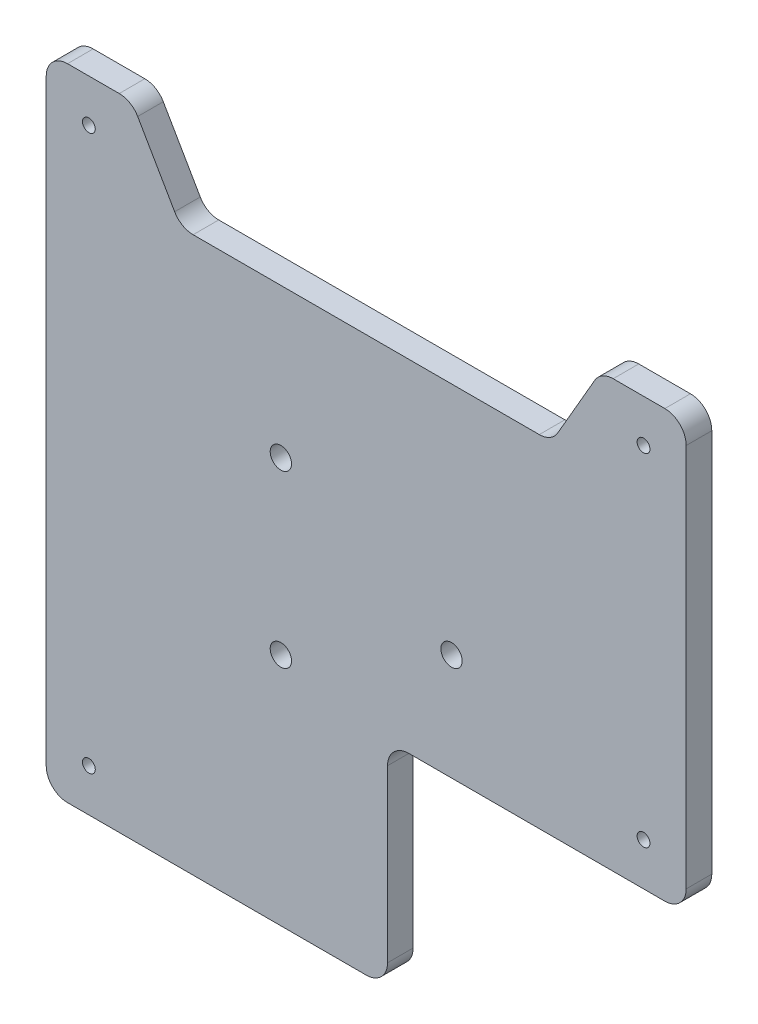
SolidWorks part; units mm, degrees
ref_plane "Plano frontal" through (0, 0, 0) normal (0, 0, 1) x (1, 0, 0)
ref_plane "Plano superior" through (0, 0, 0) normal (0, 1, 0) x (1, 0, 0)
ref_plane "Plano direito" through (0, 0, 0) normal (1, 0, 0) x (0, 0, -1)
sketch "Esboço1" plane through (0, 0, 0) normal (0, 0, 1) x (1, 0, 0)
  line L1 (-138.7501, 120.054) -> (11.2499, 120.054)
  line L2 (-138.7501, 120.054) -> (-138.7501, -29.946)
  line L3 (-138.7501, -29.946) -> (11.2499, -29.946)
  line L4 (11.2499, 120.054) -> (11.2499, -29.946)
  line L5 (-138.7501, 120.054) -> (11.2499, -29.946) construction
  line L6 (-138.7501, -29.946) -> (11.2499, 120.054) construction
  line L7 (-83.7501, 65.054) -> (-43.7501, 65.054) construction
  line L8 (-83.7501, 65.054) -> (-83.7501, 25.054) construction
  line L9 (-83.7501, 25.054) -> (-43.7501, 25.054) construction
  line L10 (-43.7501, 65.054) -> (-43.7501, 25.054) construction
  line L11 (-83.7501, 65.054) -> (-43.7501, 25.054) construction
  line L12 (-83.7501, 25.054) -> (-43.7501, 65.054) construction
  circle A0 centre (-83.7501, 65.054) radius 2.5
  circle A3 centre (-83.7501, 25.054) radius 2.5
  circle A4 centre (-43.7501, 45.054) radius 2.5
  point P0 (-63.7501, 45.054)
  dimension "D4" = 5
  dimension "D1" = 150
  dimension "D2" = 40
  dimension "D3" = 40
extrude "Ressalto-extrusão1" add sketch "Esboço1" along normal blind 6
ref_axis "Eixo1" through (-83.7501, 65.054, 6) along (0, 0, -1)
ref_axis "Eixo2" through (-83.7501, 25.054, 6) along (0, 0, -1)
ref_axis "Eixo3" through (-43.7501, 45.054, 6) along (0, 0, -1)
ref_plane "Plano1" through (-83.7501, 0, 0) normal (-1, 0, 0) x (0, 0, 1)
ref_plane "Plano2" through (-43.7501, 0, 0) normal (-1, 0, 0) x (0, 0, 1)
ref_plane "Plano3" through (-63.7501, 0, 0) normal (-1, 0, 0) x (0, 0, 1)
sketch "Esboço2" plane through (0, 0, 6) normal (0, 0, 1) x (1, 0, 0)
  line L2 (11.2499, 100.054) -> (-138.7501, 100.054)
  line L3 (11.2499, 100.054) -> (-138.7501, 100.054) construction
  line L5 (-118.7501, 120.054) -> (-118.7501, -29.946)
  line L6 (-118.7501, 120.054) -> (-118.7501, -29.946) construction
  line L7 (-8.7501, 120.054) -> (-20.2971, 100.054)
  line L8 (-8.7501, -29.946) -> (-8.7501, 120.054)
  line L9 (-8.7501, -29.946) -> (-8.7501, 120.054) construction
  line L10 (-118.7501, 120.054) -> (-107.2031, 100.054)
  line L11 (-20.2971, 100.054) -> (-107.2031, 100.054)
  line L12 (-8.7501, 120.054) -> (-118.7501, 120.054)
  dimension "D4" = 30
  dimension "D5" = 30
  dimension "D1" = 20
  dimension "D2" = 20
  dimension "D3" = 20
extrude "Corte-extrusão1" cut sketch "Esboço2" against normal up to surface (6 mm away) up to face at (-63.7501, 45.054, 0)
sketch "Esboço3" plane through (0, 0, 6) normal (0, 0, 1) x (1, 0, 0)
  line L2 (-138.7501, 20.054) -> (11.2499, 20.054)
  line L3 (-138.7501, 20.054) -> (11.2499, 20.054) construction
  line L5 (-58.7501, -29.946) -> (-58.7501, 120.054)
  line L6 (-58.7501, -29.946) -> (-58.7501, 120.054) construction
  line L7 (-58.7501, 20.054) -> (11.2499, 20.054)
  line L8 (-58.7501, 20.054) -> (-58.7501, -29.946)
  line L9 (-58.7501, -29.946) -> (11.2499, -29.946)
  line L10 (11.2499, 20.054) -> (11.2499, -29.946)
  dimension "D1" = 50
  dimension "D2" = 70
extrude "Corte-extrusão2" cut sketch "Esboço3" against normal up to surface (6 mm away) up to face at (-63.7501, 77.554, 0)
fillet "Filete1" radius 5 10 edges at (11.2499, 20.054, 3) (-138.7501, -29.946, 3) (11.2499, 120.054, 3) (-138.7501, 120.054, 3) (-58.7501, -29.946, 3) (-58.7501, 20.054, 3) (-118.7501, 120.054, 3) (-20.2971, 100.054, 3) (-107.2031, 100.054, 3) (-8.7501, 120.054, 3)
sketch "Esboço4" plane through (0, 0, 6) normal (0, 0, 1) x (1, 0, 0)
  line L20 (-128.7501, -19.946) -> (-68.7501, -19.946)
  line L21 (-68.7501, -19.946) -> (-68.7501, 15.054)
  line L22 (-53.7501, 30.054) -> (1.2499, 30.054)
  line L23 (1.2499, 30.054) -> (1.2499, 110.054)
  line L24 (1.2499, 110.054) -> (-2.9766, 110.054)
  line L25 (-2.9766, 110.054) -> (-10.1935, 97.554)
  line L26 (-23.1839, 90.054) -> (-104.3164, 90.054)
  line L27 (-117.3067, 97.554) -> (-124.5236, 110.054)
  line L28 (-124.5236, 110.054) -> (-128.7501, 110.054)
  line L29 (-128.7501, 110.054) -> (-128.7501, -19.946)
  line L30 (-128.7501, -19.946) -> (-68.7501, -19.946) construction
  line L31 (-68.7501, -19.946) -> (-68.7501, 15.054) construction
  line L32 (-53.7501, 30.054) -> (1.2499, 30.054) construction
  line L33 (1.2499, 30.054) -> (1.2499, 110.054) construction
  line L34 (1.2499, 110.054) -> (-2.9766, 110.054) construction
  line L35 (-2.9766, 110.054) -> (-10.1935, 97.554) construction
  line L36 (-23.1839, 90.054) -> (-104.3164, 90.054) construction
  line L37 (-117.3067, 97.554) -> (-124.5236, 110.054) construction
  line L38 (-124.5236, 110.054) -> (-128.7501, 110.054) construction
  line L39 (-128.7501, 110.054) -> (-128.7501, -19.946) construction
  circle A10 centre (1.2499, 110.054) radius 1.5
  circle A11 centre (1.2499, 30.054) radius 1.5
  circle A12 centre (-128.7501, 110.054) radius 1.5
  circle A13 centre (-128.7501, -19.946) radius 1.5
  arc A20 (-53.7501, 30.054) -> (-68.7501, 15.054) centre (-53.7501, 15.054) ccw
  arc A21 (-23.1839, 90.054) -> (-10.1935, 97.554) centre (-23.1839, 105.054) ccw
  arc A22 (-117.3067, 97.554) -> (-104.3164, 90.054) centre (-104.3164, 105.054) ccw
  arc A23 (-53.7501, 30.054) -> (-68.7501, 15.054) centre (-53.7501, 15.054) ccw construction
  arc A24 (-23.1839, 90.054) -> (-10.1935, 97.554) centre (-23.1839, 105.054) ccw construction
  arc A25 (-117.3067, 97.554) -> (-104.3164, 90.054) centre (-104.3164, 105.054) ccw construction
  dimension "D2" = 3
  dimension "D1" = 10
extrude "Corte-extrusão3" cut sketch "Esboço4" against normal up to surface (6 mm away) up to face at (-62.7501, 66.054, 0)
